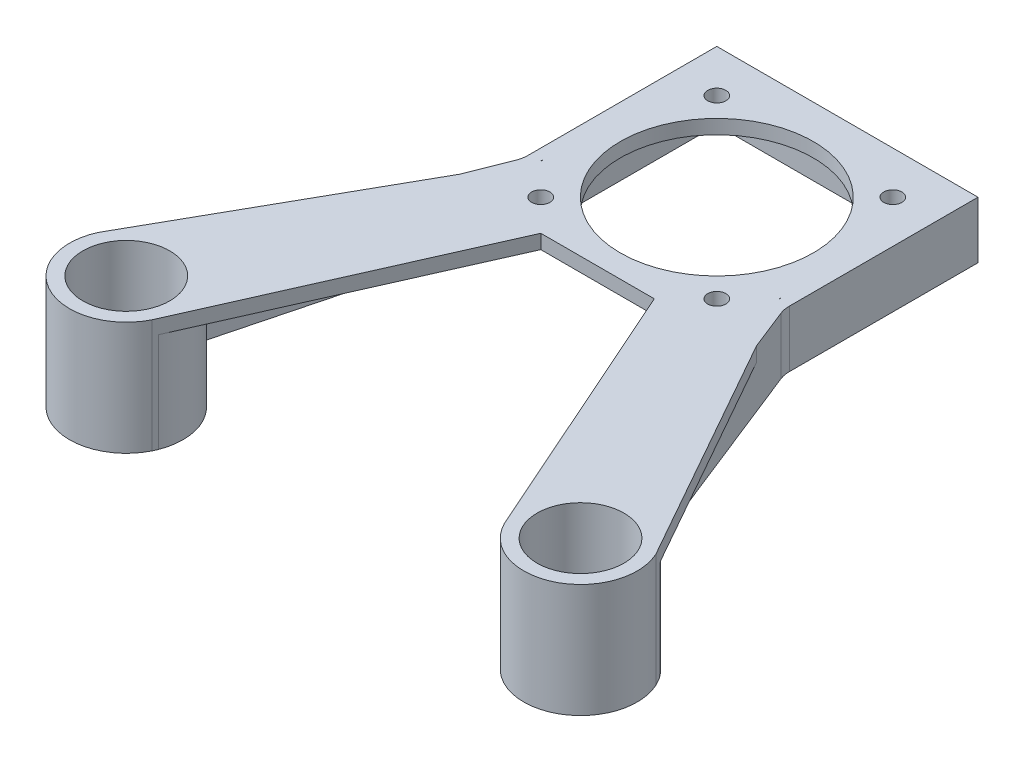
SolidWorks part; units mm, degrees
ref_plane "前视基准面" through (0, 0, 0) normal (0, 0, 1) x (1, 0, 0)
ref_plane "上视基准面" through (0, 0, 0) normal (0, 1, 0) x (1, 0, 0)
ref_plane "右视基准面" through (0, 0, 0) normal (1, 0, 0) x (0, 0, -1)
sketch "草图6" plane through (0, 0, 0) normal (0, 1, 0) x (1, 0, 0)
  line L1 (-21, -21) -> (21, -21)
  line L2 (-21, -21) -> (-21, 21)
  line L3 (-21, 21) -> (21, 21)
  line L4 (21, -21) -> (21, 21)
  line L5 (0, 21) -> (0, -21) construction
  line L6 (-21, 0) -> (21, 0) construction
  circle A0 centre (15.5, 15.5) radius 1.6
  circle A1 centre (-15.5, 15.5) radius 1.6
  circle A2 centre (-15.5, -15.5) radius 1.6
  circle A3 centre (15.5, -15.5) radius 1.6
  circle A4 centre (0, 0) radius 17
  point P0 (0, 0)
extrude "凸台-拉伸1" add sketch "草图6" along normal blind 2.5
sketch "草图7" plane through (0, 2.5, 0) normal (0, 1, 0) x (1, 0, 0)
  line L2 (21, -10) -> (49.0892, -59.8303)
  line L4 (-10, -21) -> (-31.0355, -68.4315)
  line L5 (-21, -10) -> (-49.0892, -59.8303)
  line L6 (10, -21) -> (31.0355, -68.4315)
  circle A0 centre (-40, -64) radius 10
  circle A1 centre (40, -64) radius 10
  circle A2 centre (-40, -64) radius 7.65
  circle A3 centre (40, -64) radius 7.65
  line M9 (21, -21) -> (21, 21)
  line M11 (-21, 21) -> (-21, -21)
  line M12 (-21, -21) -> (21, -21)
extrude "凸台-拉伸5" add sketch "草图7" against normal blind 2.5 contours A1 L2 L6 M9 M12 | A0 L4 L5 M12 M11 | A1 A3 | A0 A2 region at (-27.3301, 2.5, 38.6598) region at (27.3301, 2.5, 38.6598) region at (48.4348, 2.5, 59.2453) region at (-31.1252, 2.5, 67.9359)
extrude "凸台-拉伸7" add sketch "草图7<7>" against normal blind 20 contours A1 A3 region at (48.4348, 2.5, 59.2453)
sketch "草图7<7>" plane through (0, 2.5, 0) normal (0, 1, 0) x (1, 0, 0) same geometry as "草图7"
extrude "凸台-拉伸8" add sketch "草图7<8>" against normal blind 20 contours A0 A2 region at (-31.1252, 2.5, 67.9359)
sketch "草图7<8>" plane through (0, 2.5, 0) normal (0, 1, 0) x (1, 0, 0) same geometry as "草图7"
ref_plane "基准面1" through (0, 2.5, 0) normal (0, 1, 0) x (1, 0, 0)
sketch "草图9" plane through (0, 2.5, 0) normal (0, 1, 0) x (1, 0, 0)
  line L6 (0, 23) -> (-23, 23)
  line L7 (-23, 23) -> (-23, -10.2241)
  line L8 (0, 23) -> (23, 23)
  line L9 (23, 23) -> (23, -10.2241)
  line L10 (-23.3528, -12.0691) -> (-40, -54)
  line L11 (21, -9.361) -> (21, 21)
  line L12 (21, 21) -> (-21, 21)
  line L13 (-21, 21) -> (-21, -9.361)
  line L14 (-21.1607, -10.6185) -> (-33.1409, -56.7232)
  line L15 (23.3528, -12.0691) -> (40, -54)
  line L16 (21.1607, -10.6185) -> (33.1409, -56.7232)
  arc A0 (-30.6977, -67.6697) -> (-48.2732, -58.3826) centre (-40, -64) ccw construction
  arc A1 (-30.6977, -67.6697) -> (-48.2732, -58.3826) centre (-40, -64) ccw construction
  arc A2 (48.2732, -58.3826) -> (30.6977, -67.6697) centre (40, -64) ccw construction
  arc A3 (48.2732, -58.3826) -> (30.6977, -67.6697) centre (40, -64) ccw construction
  arc A4 (23, -10.2241) -> (23.3528, -12.0691) centre (28, -10.2241) ccw
  arc A5 (21, -9.361) -> (21.1607, -10.6185) centre (26, -9.361) ccw
  arc A6 (-21, -9.361) -> (-21.1607, -10.6185) centre (-26, -9.361) cw
  arc A7 (-23, -10.2241) -> (-23.3528, -12.0691) centre (-28, -10.2241) cw
  arc A8 (-33.1409, -56.7232) -> (-40, -54) centre (-40, -64) ccw
  arc A9 (40, -54) -> (33.1409, -56.7232) centre (40, -64) ccw
  point P45 (21, -10)
  point P48 (-21, -10)
  dimension "D4" = 5
extrude "凸台-拉伸12" add sketch "草图9" against normal blind 10 contours L8 L9 A4 L15 A9 L16 A5 L11 L12 L13 A6 L14 A8 L10 A7 L7 L6
